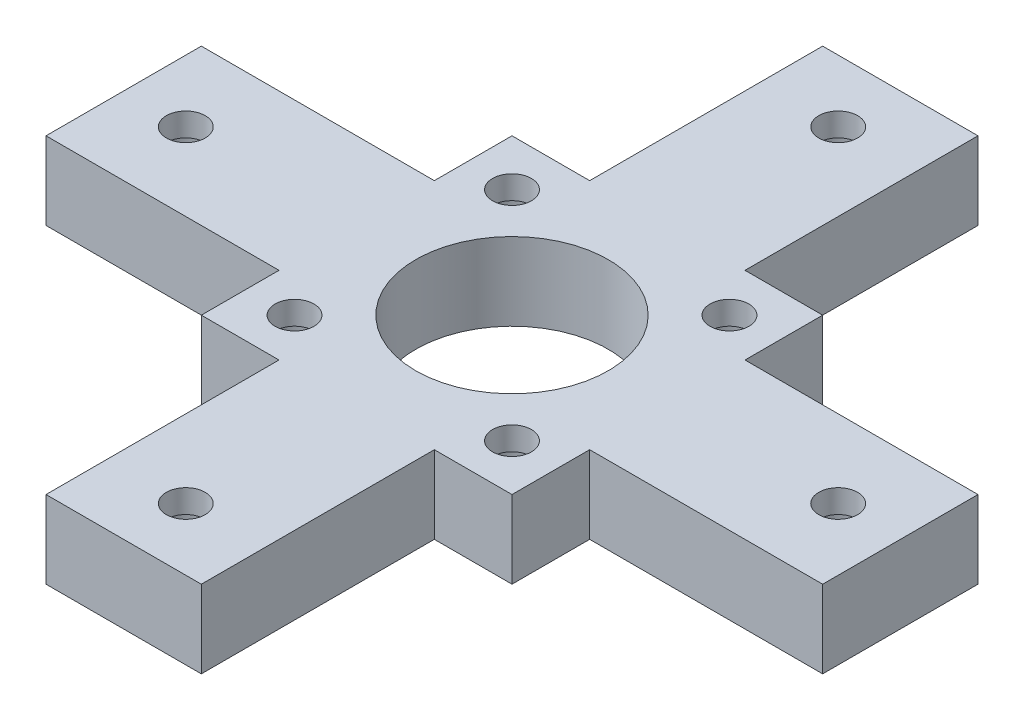
SolidWorks part; units mm, degrees
ref_plane "前视基准面" through (0, 0, 0) normal (0, 0, 1) x (1, 0, 0)
ref_plane "上视基准面" through (0, 0, 0) normal (0, 1, 0) x (1, 0, 0)
ref_plane "右视基准面" through (0, 0, 0) normal (1, 0, 0) x (0, 0, -1)
other "Configuration Table"
sketch "草图1" plane through (0, 0, 0) normal (0, 1, 0) x (1, 0, 0)
  line L1 (-10, 10) -> (10, 10)
  line L2 (-10, 10) -> (-10, -10)
  line L3 (-10, -10) -> (10, -10)
  line L4 (10, 10) -> (10, -10)
  line L5 (-25, 5) -> (-10, 5)
  line L6 (-25, 5) -> (-25, -5)
  line L7 (-25, -5) -> (-10, -5)
  line L8 (-10, 5) -> (-10, -5)
  line L9 (-5, -10) -> (5, -10)
  line L10 (-5, -10) -> (-5, -25)
  line L11 (-5, -25) -> (5, -25)
  line L12 (5, -10) -> (5, -25)
  line L13 (-5, 25) -> (5, 25)
  line L14 (-5, 25) -> (-5, 10)
  line L15 (-5, 10) -> (5, 10)
  line L16 (5, 25) -> (5, 10)
  line L17 (25, -5) -> (10, -5)
  line L18 (25, -5) -> (25, 5)
  line L19 (25, 5) -> (10, 5)
  line L20 (10, -5) -> (10, 5)
  circle A11 centre (0, 0) radius 6.2
  point P11 (-25, 0)
  point P16 (0, -25)
  dimension "D3" = 10
  dimension "D4" = 10
  dimension "D1" = 10
  dimension "D2" = 10
  dimension "D5" = 12.4
  dimension "D6" = 10
  dimension "D7" = 15
extrude "凸台-拉伸1" add sketch "草图1" along normal blind 5 contours L16 L13 L14 L1 | L6 L7 L2 L5 | L12 L3 L10 L11 | L18 L19 L4 L17 | L3 L4 L1 L2 | A11 region at (0, 0, -17.5) region at (-17.5, 0, 0) region at (17.5, 0, 0) region at (0, 0, 17.5)
sketch "草图2" plane through (0, 0, 0) normal (0, -1, 0) x (1, 0, 0)
  line L0 (-21, 0) -> (0, 0) construction
  line L1 (0, 0) -> (21, 0) construction
  line L2 (0, 21) -> (0, 0) construction
  line L3 (0, 0) -> (0, -21) construction
  line L4 (-10, -10) -> (-5, -10) construction
  line L5 (-10, -10) -> (-10, -5) construction
  line L6 (10, 5) -> (10, 10) construction
  line L7 (5, 10) -> (10, 10) construction
  circle A0 centre (7, 7) radius 2
  circle A1 centre (7, -7) radius 2
  circle A2 centre (-7, 7) radius 2
  circle A3 centre (-7, -7) radius 2
  circle A4 centre (7, 7) radius 1.25
  circle A5 centre (7, -7) radius 1.25
  circle A6 centre (-7, -7) radius 1.25
  circle A7 centre (-7, 7) radius 1.25
  circle A8 centre (0, 21) radius 2
  circle A9 centre (0, 21) radius 1.25
  circle A10 centre (21, 0) radius 1.25
  circle A11 centre (21, 0) radius 2
  circle A12 centre (0, -21) radius 1.25
  circle A13 centre (0, -21) radius 2
  circle A14 centre (-21, 0) radius 1.25
  circle A15 centre (-21, 0) radius 2
  point P32 (0, 15.1966)
  dimension "D1" = 4
  dimension "D2" = 2.5
  dimension "D8" = 2.5
  dimension "D9" = 4
  dimension "D3" = 3
  dimension "D4" = 3
  dimension "D5" = 3
  dimension "D6" = 3
  dimension "D7" = 21
extrude "切除-拉伸1" cut sketch "草图2" against normal through all contours A4 | A5 | A6 | A7 | A14 | A9 | A10 | A12
extrude "切除-拉伸2" cut sketch "草图2<3>" against normal offset from surface (3.5 mm away) 1.5 up to face at (7, 5, -8.25)
sketch "草图2<3>" plane through (0, 0, 0) normal (0, -1, 0) x (1, 0, 0) same geometry as "草图2"
